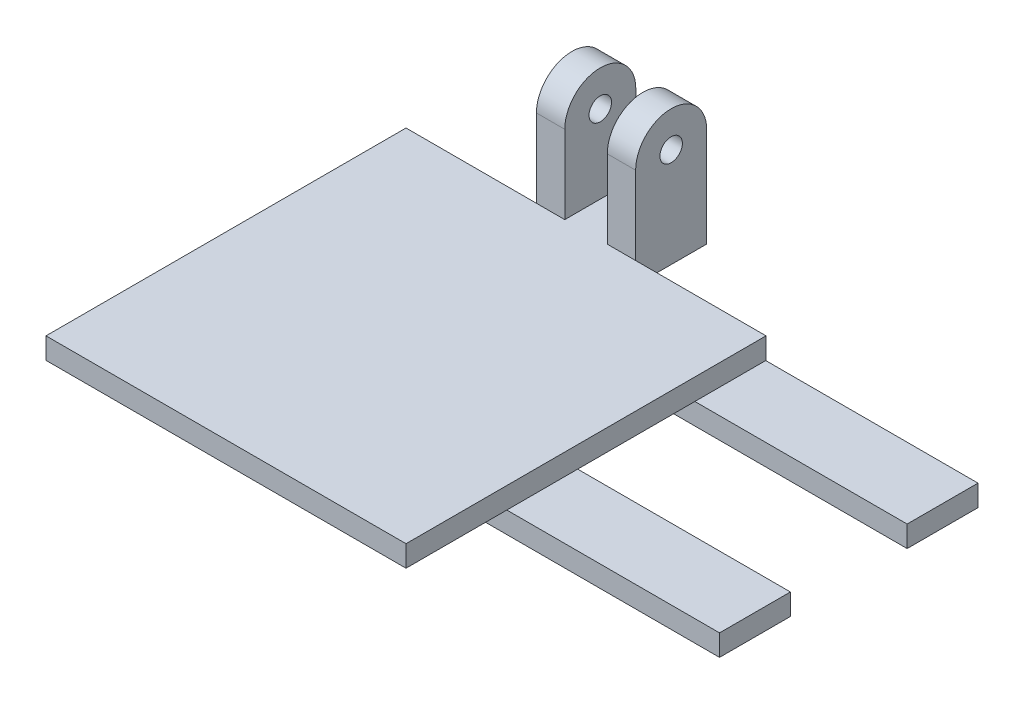
SolidWorks part; units mm, degrees
ref_plane "Front Plane" through (0, 0, 0) normal (0, 0, 1) x (1, 0, 0)
ref_plane "Top Plane" through (0, 0, 0) normal (0, 1, 0) x (1, 0, 0)
ref_plane "Right Plane" through (0, 0, 0) normal (1, 0, 0) x (0, 0, -1)
sketch "Sketch1" plane through (0, 0, 0) normal (0, 1, 0) x (1, 0, 0)
  line L1 (0, 0) -> (50.8, 0)
  line L2 (0, 0) -> (0, 50.8)
  line L3 (0, 50.8) -> (50.8, 50.8)
  line L4 (50.8, 0) -> (50.8, 50.8)
  line L5 (18.4, 50.8) -> (32.4, 50.8)
  line L6 (18.4, 50.8) -> (18.4, 60.8232)
  line L7 (18.4, 60.8232) -> (32.4, 60.8232)
  line L8 (32.4, 50.8) -> (32.4, 60.8232)
  line L9 (18.4, 50.8) -> (22.4, 50.8)
  line L10 (18.4, 50.8) -> (18.4, 60.8232)
  line L11 (18.4, 60.8232) -> (22.4, 60.8232)
  line L12 (22.4, 50.8) -> (22.4, 60.8232)
  line L13 (32.4, 50.8) -> (28.4, 50.8)
  line L14 (32.4, 50.8) -> (32.4, 60.8232)
  line L15 (32.4, 60.8232) -> (28.4, 60.8232)
  line L16 (28.4, 50.8) -> (28.4, 60.8232)
  dimension "D1" = 50.8
  dimension "D2" = 50.8
  dimension "D3" = 14
  dimension "D4" = 18.4
  dimension "D5" = 4
  dimension "D6" = 4
extrude "Boss-Extrude1" add sketch "Sketch1" along normal blind 3 contours L1 L4 L3 L5 L2 | L5 L16 L7 L12 region at (25.4, 0, -25.4) region at (25.4, 0, -55.8116)
extrude "Boss-Extrude2" add sketch "Sketch1<3>" along normal blind 19.05 contours L16 L3 L8 L7 | L3 L12 L7 L6 region at (20.4, 0, -55.8116) region at (30.4, 0, -55.8116)
sketch "Sketch1<3>" plane through (0, 0, 0) normal (0, 1, 0) x (1, 0, 0) same geometry as "Sketch1"
sketch "Sketch2" plane through (32.4, 0, 0) normal (1, 0, 0) x (0, 0, -1)
  line L0 (50.8, 14.0384) -> (49.9115, 20.3951)
  line L1 (60.8232, 19.05) -> (60.8232, 0) construction
  line L2 (49.9115, 20.3951) -> (64.5018, 21.2477)
  line L3 (50.8, 19.05) -> (50.8, 3) construction
  line L4 (64.5018, 21.2477) -> (60.8232, 14.0384)
  arc A0 (50.8, 14.0384) -> (60.8232, 14.0384) centre (55.8116, 14.0384) cw
  circle A1 centre (55.8116, 14.0384) radius 1.5875
  dimension "D1" = 3.175
extrude "Cut-Extrude1" cut sketch "Sketch2" against normal blind 19.05
sketch "Sketch3" plane through (0, 0, 0) normal (0, -1, 0) x (1, 0, 0)
  line L0 (30.0172, -14.2228) -> (0.0172, -14.2228)
  line L1 (0.0172, -14.2228) -> (0.0172, -24.2228)
  line L2 (0.0172, -24.2228) -> (80.8172, -24.2228)
  line L4 (80.8172, -24.2228) -> (80.8172, -14.2228)
  line L5 (80.8172, -14.2228) -> (30.0172, -14.2228)
  line L7 (80.7529, -40.7574) -> (-0.0435, -40.7574)
  line L8 (80.7529, -40.7574) -> (80.7529, -50.7574)
  line L9 (80.7529, -50.7574) -> (-0.0435, -50.7574)
  line L10 (-0.0435, -40.7574) -> (-0.0435, -50.7574)
  dimension "D1" = 30
  dimension "D2" = 10
  dimension "D3" = 10
  dimension "D4" = 80.8
  dimension "D5" = 80.7964
extrude "Boss-Extrude3" add sketch "Sketch3" along normal blind 3
